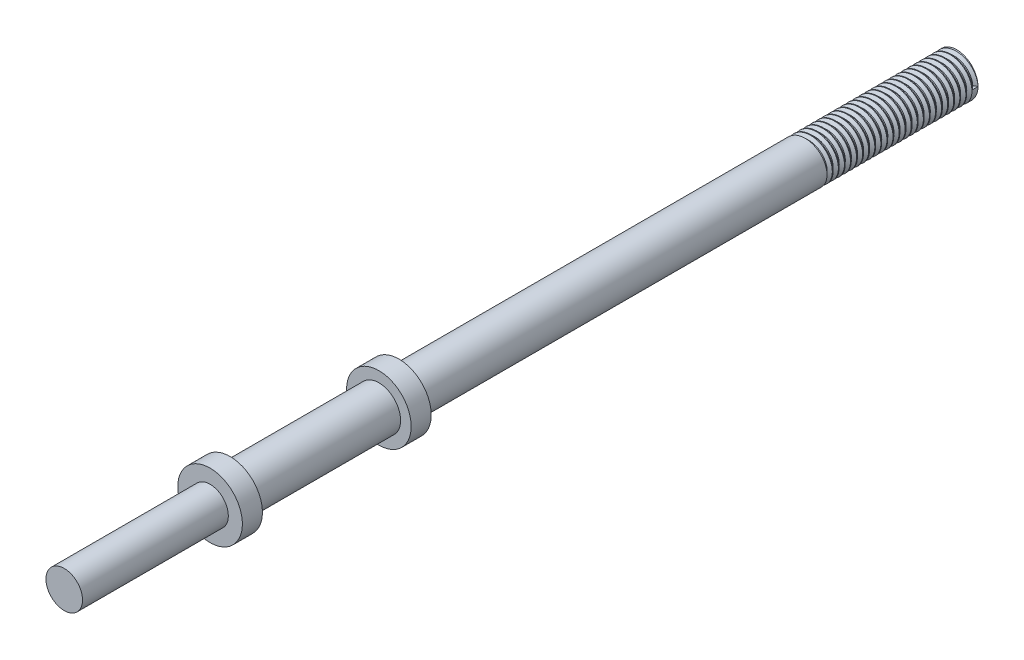
SolidWorks part; units mm, degrees
ref_plane "Front Plane" through (0, 0, 0) normal (0, 0, 1) x (1, 0, 0)
ref_plane "Top Plane" through (0, 0, 0) normal (0, 1, 0) x (1, 0, 0)
ref_plane "Right Plane" through (0, 0, 0) normal (1, 0, 0) x (0, 0, -1)
sketch "Sketch1" plane through (0, 0, 0) normal (0, 0, 1) x (1, 0, 0)
  circle A0 centre (0, 0) radius 3.175
extrude "Boss-Extrude1" add sketch "Sketch1" along normal blind 83.3438
sketch "Sketch2" plane through (0, 0, 83.3438) normal (0, 0, 1) x (1, 0, 0)
  circle A0 centre (0, 0) radius 4.826
extrude "Boss-Extrude2" add sketch "Sketch2" along normal blind 2.9972
sketch "Sketch3" plane through (0, 0, 86.341) normal (0, 0, 1) x (1, 0, 0)
  circle A0 centre (0, 0) radius 3.2512
extrude "Boss-Extrude3" add sketch "Sketch3" along normal blind 22.225
sketch "Sketch4" plane through (0, 0, 108.566) normal (0, 0, 1) x (1, 0, 0)
  circle A0 centre (0, 0) radius 4.826
extrude "Boss-Extrude4" add sketch "Sketch4" along normal blind 2.9972
sketch "Sketch5" plane through (0, 0, 111.5631) normal (0, 0, 1) x (1, 0, 0)
  circle A0 centre (0, 0) radius 2.7305
extrude "Boss-Extrude5" add sketch "Sketch5" along normal blind 21.7866
thread "Thread1" pitch 0.9071 method cut profile "Thread Profile1" start angle 0, offset 0, length 22.225, pitch 0.9071, diameter 6.35
ref_plane "Plane1" through (3.175, 0, 0) normal (0, -1, 0) x (1, 0, 0)
sketch "Thread Profile1" plane through (3.175, 0, 0) normal (0, -1, 0) x (1, 0, 0)
  line L0 (0, 0) -> (0, 0.9071) construction
  line L11 (0, 0) -> (0, 0.7937)
  line L12 (0, 0.7937) -> (-0.491, 0.5103)
  line L13 (-0.491, 0.5103) -> (-0.491, 0.2835)
  line L15 (-0.491, 0.2835) -> (0, 0)
  line L17 (-0.491, 0.3969) -> (0, 0.3969) construction
  point P2 (0, 0)
  dimension "Pitch" = 0.9071
  dimension "Profile_Angle" = 60
  dimension "Profile_Land" = 0.2268
  dimension "Profile_Height" = 0.491
